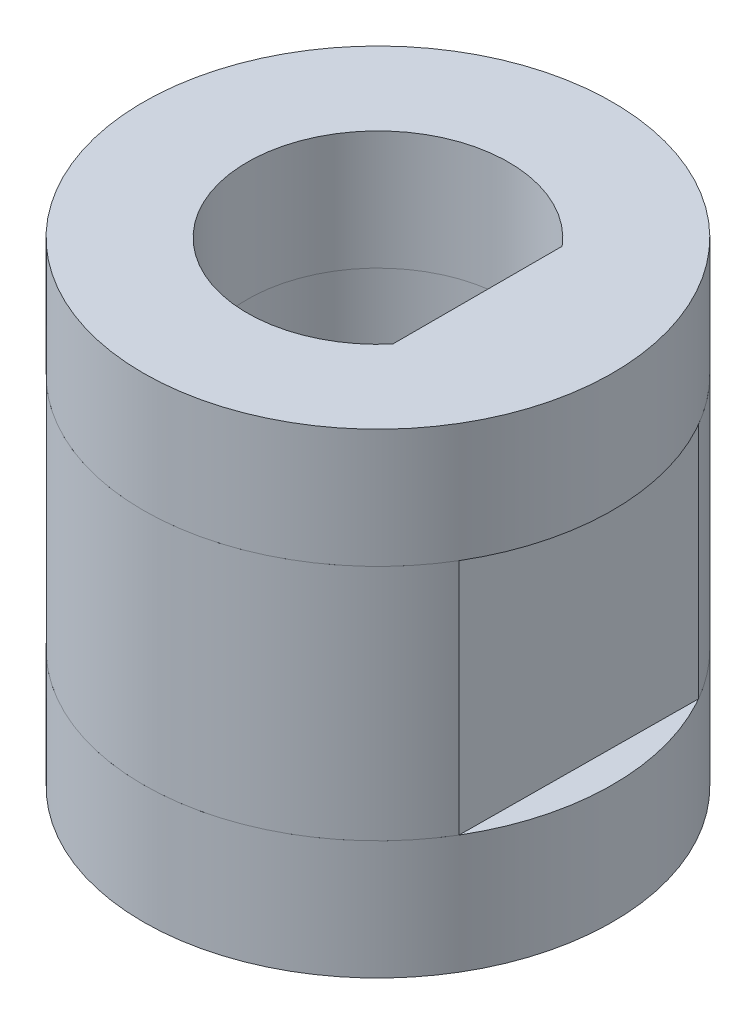
SolidWorks part; units mm, degrees
ref_plane "Front Plane" through (0, 0, 0) normal (0, 0, 1) x (1, 0, 0)
ref_plane "Top Plane" through (0, 0, 0) normal (0, 1, 0) x (1, 0, 0)
ref_plane "Right Plane" through (0, 0, 0) normal (1, 0, 0) x (0, 0, -1)
sketch "Sketch1" plane through (0, 0, 0) normal (0, 1, 0) x (1, 0, 0)
  circle A0 centre (0, 0) radius 3.95
  dimension "D1" = 7.9
extrude "Boss-Extrude1" add sketch "Sketch1" along normal blind 2 contours A0
sketch "Sketch3" plane through (0, 2, 0) normal (0, 1, 0) x (1, 0, 0)
  line L2 (-2.0256, 3.3911) -> (1.9744, 3.4212)
  line L3 (3.4212, 1.9744) -> (3.3911, -2.0256)
  arc A2 (-2.0256, 3.3911) -> (3.3911, -2.0256) centre (0, 0) ccw
  arc A3 (3.4212, 1.9744) -> (1.9744, 3.4212) centre (0, 0) ccw
  point P3 (3.4212, 1.9744)
  point P4 (3.3911, -2.0256)
  point P5 (1.9744, 3.4212)
  point P6 (-2.0256, 3.3911)
  dimension "D3" = 3.95
  dimension "D1" = 4
  dimension "D2" = 4
extrude "Boss-Extrude2" add sketch "Sketch3" along normal blind 4
sketch "Sketch4" plane through (0, 6, 0) normal (0, 1, 0) x (1, 0, 0)
  circle A0 centre (0, 0) radius 3.95
  dimension "D1" = 7.9
extrude "Boss-Extrude3" add sketch "Sketch4" along normal blind 2
sketch "Sketch5" plane through (0, 8, 0) normal (0, 1, 0) x (1, 0, 0)
  line L0 (-2.2, 0) -> (1.6762, 0) construction
  line L2 (1.6762, 1.4249) -> (1.6762, -1.4249)
  arc A1 (1.6762, 1.4249) -> (1.6762, -1.4249) centre (0, 0) ccw
  dimension "D1" = 2.2
extrude "Cut-Extrude1" cut sketch "Sketch5" against normal through all
